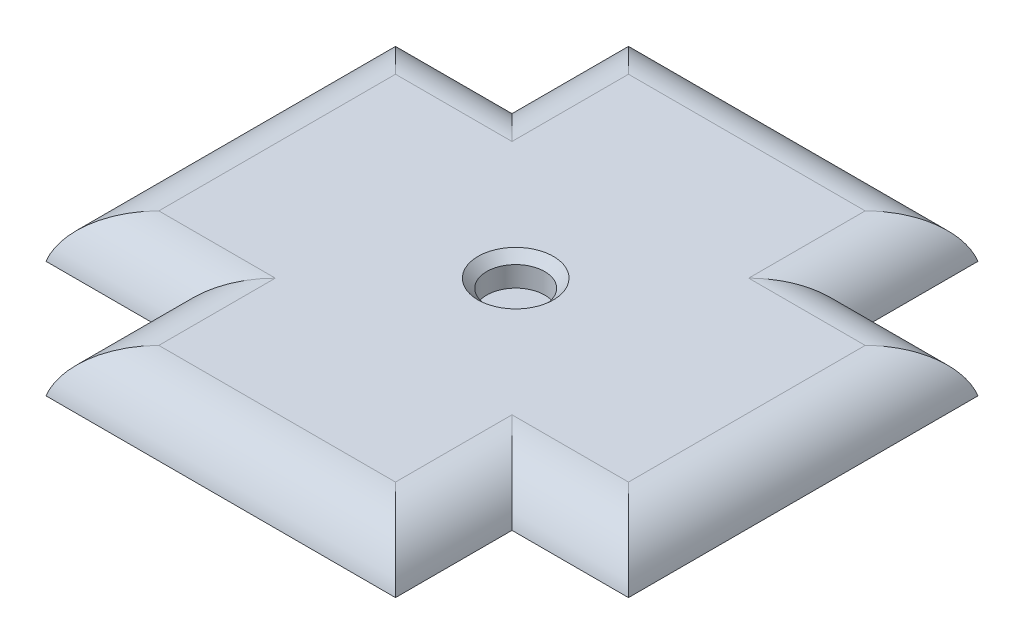
SolidWorks part; units mm, degrees
ref_plane "Front Plane" through (0, 0, 0) normal (0, 0, 1) x (1, 0, 0)
ref_plane "Top Plane" through (0, 0, 0) normal (0, 1, 0) x (1, 0, 0)
ref_plane "Right Plane" through (0, 0, 0) normal (1, 0, 0) x (0, 0, -1)
sketch "Sketch1" plane through (0, 0, 0) normal (0, 1, 0) x (1, 0, 0)
  line L1 (0, 0) -> (100, 0)
  line L2 (0, 0) -> (0, -100)
  line L3 (0, -100) -> (100, -100)
  line L4 (100, 0) -> (100, -100)
  line L5 (80, 0) -> (100, 0)
  line L6 (80, 0) -> (80, -20)
  line L7 (80, -20) -> (100, -20)
  line L8 (100, 0) -> (100, -20)
  line L9 (0, 0) -> (20, 0)
  line L10 (0, 0) -> (0, -20)
  line L11 (0, -20) -> (20, -20)
  line L12 (20, 0) -> (20, -20)
  line L13 (0, -100) -> (20, -100)
  line L14 (0, -100) -> (0, -80)
  line L15 (0, -80) -> (20, -80)
  line L16 (20, -100) -> (20, -80)
  line L17 (100, -100) -> (80, -100)
  line L18 (100, -100) -> (100, -80)
  line L19 (100, -80) -> (80, -80)
  line L20 (80, -100) -> (80, -80)
  dimension "D1" = 100
  dimension "D2" = 100
  dimension "D3" = 20
  dimension "D4" = 20
  dimension "D5" = 20
  dimension "D6" = 20
  dimension "D7" = 20
  dimension "D8" = 20
  dimension "D9" = 20
  dimension "D10" = 20
extrude "Boss-Extrude1" add sketch "Sketch1" along normal blind 7.5 contours L3 L20 L19 L4 L7 L6 L1 L12 L11 L2 L15 L16 region at (50, 0, 50)
fillet "Fillet1" radius 10 12 edges at (10, 7.5, 80) (20, 7.5, 90) (80, 7.5, 90) (50, 7.5, 100) (90, 7.5, 80) (90, 7.5, 20) (80, 7.5, 10) (100, 7.5, 50) (50, 7.5, 0) (0, 7.5, 50) (20, 7.5, 10) (10, 7.5, 20)
sketch "Sketch2" plane through (0, 7.5, 0) normal (0, 1, 0) x (1, 0, 0)
  line L2 (90.3175, -70.3175) -> (90.3175, -29.6825) construction
  line L3 (70.3175, -9.6825) -> (29.6825, -9.6825) construction
  circle A0 centre (50.3175, -49.6825) radius 4.975
  dimension "D1" = 9.95
  dimension "D2" = 40
  dimension "D3" = 40
extrude "Cut-Extrude1" cut sketch "Sketch2" against normal blind 5 from surface starting at face at (50, 7.5, 50)
chamfer "Chamfer2" distance 1.5 angle 45 1 edges at (50.3175, 7.5, 54.6575)
